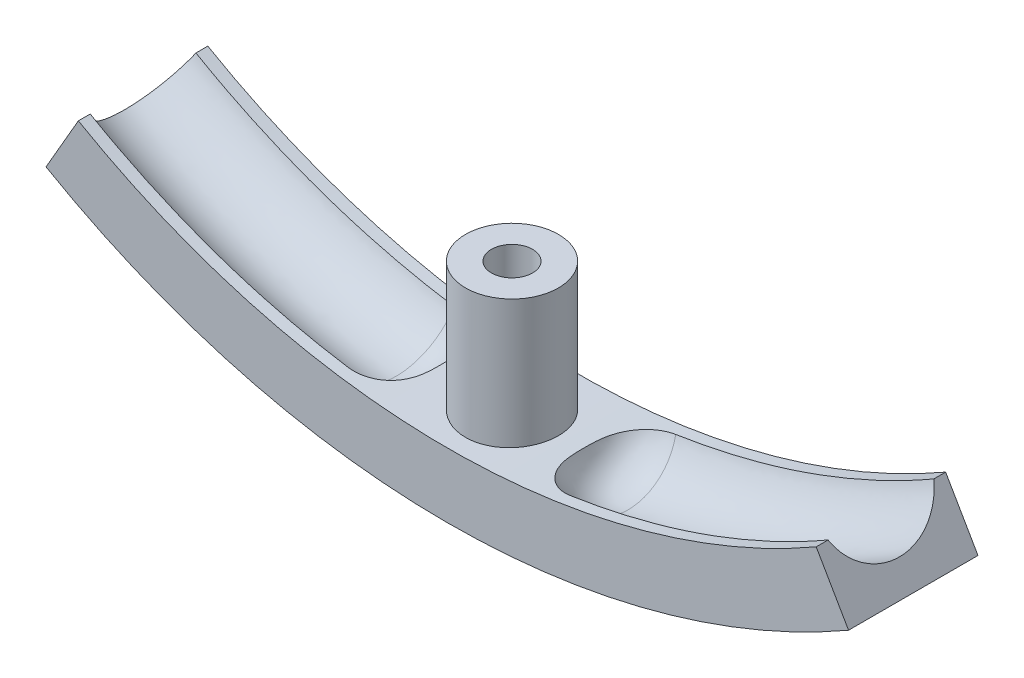
SolidWorks part; units mm, degrees
ref_plane "Front Plane" through (0, 0, 0) normal (0, 0, 1) x (1, 0, 0)
ref_plane "Top Plane" through (0, 0, 0) normal (0, 1, 0) x (1, 0, 0)
ref_plane "Right Plane" through (0, 0, 0) normal (1, 0, 0) x (0, 0, -1)
sketch "Sketch2" plane through (0, 0, 0) normal (0, 1, 0) x (1, 0, 0)
  circle A0 centre (0, 0) radius 1.5875
  circle A1 centre (0, 0) radius 3.5875
  dimension "D1" = 3.175
  dimension "D2" = 2
extrude "Boss-Extrude1" add sketch "Sketch2" against normal blind 10
sketch "Sketch4" plane through (0, 0, 0) normal (0, 0, 1) x (1, 0, 0)
  line L0 (0, -15) -> (0, -10) construction
  line L1 (-3.5875, -10) -> (3.5875, -10) construction
  line L2 (28.5, -2.3634) -> (31, -6.6936)
  line L3 (-28.5, -2.3634) -> (-31, -6.6936)
  arc A0 (-31, -6.6936) -> (31, -6.6936) centre (0, 47) ccw
  arc A1 (-28.5, -2.3634) -> (28.5, -2.3634) centre (0, 47) ccw
  dimension "D3" = 5
  dimension "D1" = 62
  dimension "D2" = 5
  dimension "D4" = 30
extrude "Boss-Extrude2" add sketch "Sketch4" along normal blind 5 and the other way blind 5
sketch "Sketch6" plane through (20.3516, 11.75, 0) normal (0.866, 0.5, 0) x (0, 0, -1)
  line L1 (5, -16.2968) -> (-5, -16.2968) construction
  circle A0 centre (0, -14.7968) radius 4.35
  dimension "D1" = 8.7
  dimension "D2" = 1.5
sketch "Sketch9" plane through (0, 0, 0) normal (0, 0, 1) x (1, 0, 0)
  arc A1 (6.023, -14.7068) -> (31, -6.6936) centre (0, 47) ccw
sweep "Cut-Sweep1" cut profiles "Sketch6" path "Sketch9"
mirror "Mirror1" about plane through (0, 0, 0) normal (1, 0, 0) of "Cut-Sweep1"
fillet "Fillet3" radius 3 2 edges at (5.8141, -12.5669, 0) (-5.8141, -12.5669, 0)
sketch "Sketch10" plane through (0, 0, 0) normal (0, 1, 0) x (1, 0, 0)
  circle A0 centre (0, 0) radius 1.5875
extrude "Cut-Extrude1" cut sketch "Sketch10" against normal through all
